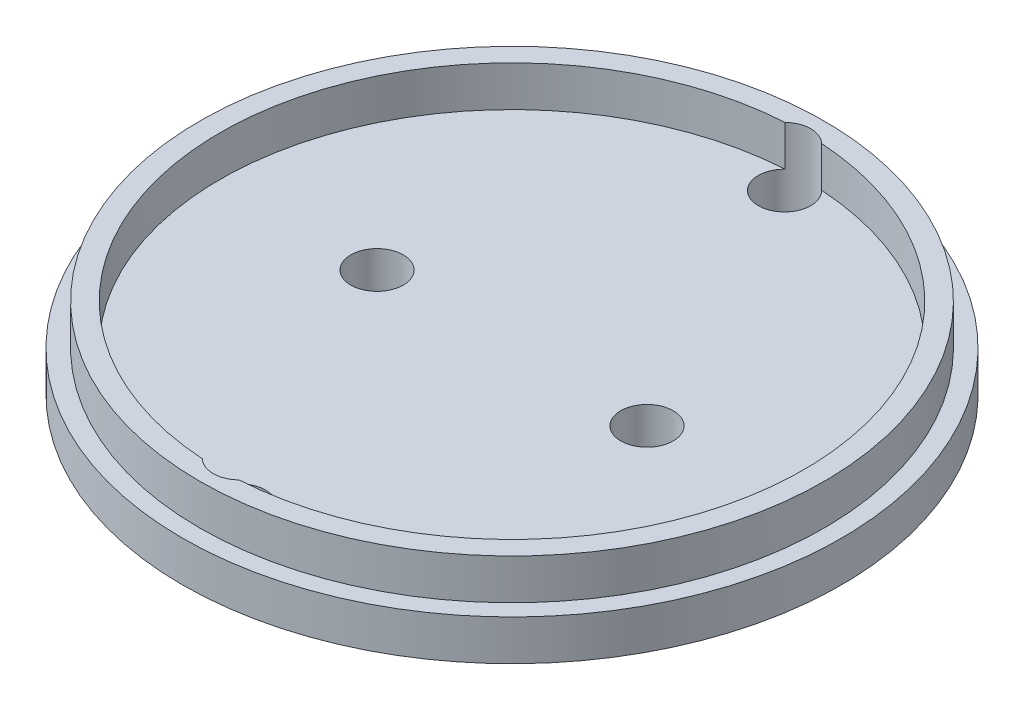
SolidWorks part; units mm, degrees
ref_plane "Front Plane" through (0, 0, 0) normal (0, 0, 1) x (1, 0, 0)
ref_plane "Top Plane" through (0, 0, 0) normal (0, 1, 0) x (1, 0, 0)
ref_plane "Right Plane" through (0, 0, 0) normal (1, 0, 0) x (0, 0, -1)
sketch "Sketch1" plane through (0, 0, 0) normal (0, 1, 0) x (1, 0, 0)
  circle A0 centre (0, 0) radius 40.7
  circle A1 centre (0, 0) radius 38.55
  circle A2 centre (0, 0) radius 36.05
  dimension "D1" = 81.4
  dimension "D2" = 2.15
  dimension "D3" = 2.5
extrude "Boss-Extrude1" add sketch "Sketch1" along normal blind 5 contours A1 A2 region at (-37.4596, 0, 0)
extrude "Boss-Extrude2" add sketch "Sketch1<4>" against normal blind 5 contours A1 A2 | A2 | A0 A1 region at (-39.5488, 0, 0) region at (-37.4596, 0, 0) region at (0, 0, 0)
sketch "Sketch1<4>" plane through (0, 0, 0) normal (0, 1, 0) x (1, 0, 0) same geometry as "Sketch1"
sketch "Sketch4" plane through (0, -5, 0) normal (0, -1, 0) x (1, 0, 0)
  line L0 (16.6687, 0) -> (-16.6688, 0) construction
  line L1 (0, 33.655) -> (0, -33.655) construction
  circle A0 centre (-16.6688, 0) radius 3.2385
  circle A1 centre (16.6687, 0) radius 3.2385
  circle A2 centre (0, 33.655) radius 3.2385
  circle A3 centre (0, -33.655) radius 3.2385
  point P5 (0, 0)
  point P11 (0, 0)
  dimension "D2" = 6.477
  dimension "D4" = 6.477
  dimension "D1" = 33.3375
  dimension "D3" = 67.31
extrude "Cut-Extrude1" cut sketch "Sketch4" against normal through all both and the other way through all
